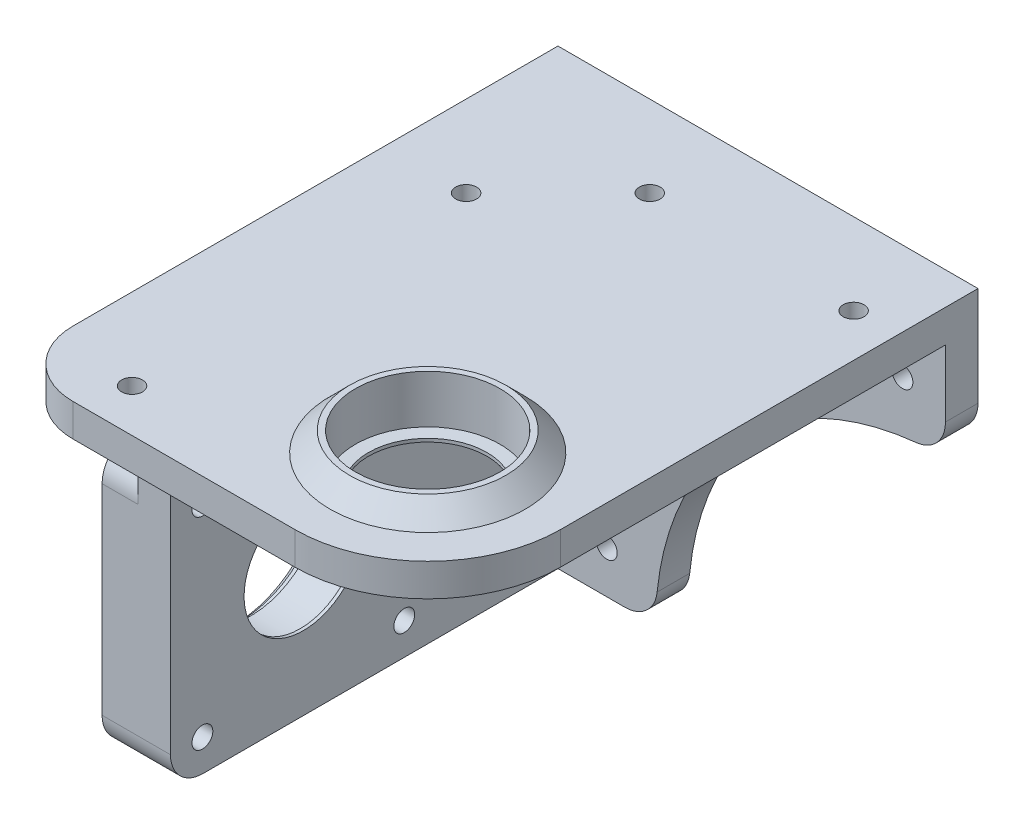
SolidWorks part; units mm, degrees
ref_plane "Front Plane" through (0, 0, 0) normal (0, 0, 1) x (1, 0, 0)
ref_plane "Top Plane" through (0, 0, 0) normal (0, 1, 0) x (1, 0, 0)
ref_plane "Right Plane" through (0, 0, 0) normal (1, 0, 0) x (0, 0, -1)
sketch "Sketch1" plane through (0, 0, 0) normal (0, 0, 1) x (1, 0, 0)
  line L0 (-1060.6916, 12.25) -> (48939.3083, 12.25) construction
  line L1 (-32.25, -32.25) -> (-16.9968, -32.25)
  line L2 (-32.25, -32.25) -> (-32.25, 32.25)
  line L3 (-32.25, 32.25) -> (32.25, 32.25)
  line L4 (32.25, 16.9968) -> (32.25, 32.25)
  line L5 (-32.25, -32.25) -> (32.25, 32.25) construction
  line L6 (-32.25, 32.25) -> (32.25, -32.25) construction
  line L7 (-12.25, -1023.3214) -> (-12.25, 48976.6786) construction
  line L8 (-1048.9078, 19.75) -> (48951.0922, 19.75) construction
  line L9 (-19.75, -955.4396) -> (-19.75, 49044.5604) construction
  arc A0 (27.7551, 12.0224) -> (-12.0224, -27.7551) centre (32.25, -32.25) ccw
  circle A1 centre (-19.75, 19.75) radius 1.6
  circle A2 centre (-5.65, 19.75) radius 1.6
  circle A3 centre (25.65, 19.75) radius 1.6
  circle A4 centre (-19.75, 5.65) radius 1.6
  circle A5 centre (-19.75, -25.65) radius 1.6
  arc A6 (27.7551, 12.0224) -> (32.25, 16.9968) centre (27.25, 16.9968) ccw
  arc A7 (-12.0224, -27.7551) -> (-16.9968, -32.25) centre (-16.9968, -27.25) cw
  point P0 (0, 0)
  point P28 (32.25, 12.25)
  point P31 (-12.25, -32.25)
  dimension "D4" = 7.5
  dimension "D6" = 3.2
  dimension "D8" = 5
  dimension "D9" = 5
  dimension "D10" = 5
  dimension "D11" = 5
  dimension "D1" = 64.5
  dimension "D2" = 20
  dimension "D3" = 20
  dimension "D5" = 7.5
  dimension "D7" = 5
extrude "Boss-Extrude1" add sketch "Sketch1" along normal blind 5
sketch "Sketch2" plane through (0, 0, 5) normal (0, 0, 1) x (1, 0, 0)
  line L0 (32.25, 16.9968) -> (32.25, 32.25) construction
  line L1 (-32.25, 32.25) -> (32.25, 32.25)
  line L2 (-32.25, 32.25) -> (-32.25, 27.25)
  line L3 (-27.25, 27.25) -> (32.25, 27.25)
  line L4 (32.25, 32.25) -> (32.25, 27.25)
  line L5 (-32.25, -32.25) -> (-16.9968, -32.25) construction
  line L7 (-32.25, 27.25) -> (-32.25, -32.25)
  line L8 (-32.25, -32.25) -> (-27.25, -32.25)
  line L9 (-27.25, 27.25) -> (-27.25, -32.25)
  dimension "D1" = 5
extrude "Boss-Extrude2" add sketch "Sketch2" along normal blind 79.5
sketch "Sketch3" plane through (0, 32.25, 0) normal (0, 1, 0) x (1, 0, 0)
  line L2 (32.25, -84.5) -> (-32.25, -84.5) construction
  line L3 (32.25, -84.5) -> (32.25, 0) construction
  line L4 (11.85, -84.5) -> (11.85, -91.4766)
  line L5 (11.85, -91.4766) -> (44.1004, -91.4766)
  line L6 (44.1004, -91.4766) -> (44.1004, -64.1)
  line L7 (44.1004, -64.1) -> (32.25, -64.1)
  circle A0 centre (11.85, -64.1) radius 15 construction
  arc A1 (11.85, -84.5) -> (32.25, -64.1) centre (11.85, -64.1) ccw
  circle A2 centre (11.85, -64.1) radius 11.1
  dimension "D1" = 30
  dimension "D2" = 5.4
  dimension "D3" = 22.2
extrude "Cut-Extrude1" cut sketch "Sketch3" against normal through all
sketch "Sketch4" plane through (0, 32.25, 0) normal (0, 1, 0) x (1, 0, 0)
  circle A0 centre (11.85, -64.1) radius 15
  circle A1 centre (11.85, -64.1) radius 15 construction
  circle A2 centre (11.85, -64.1) radius 11.1
  circle A3 centre (11.85, -64.1) radius 11.1 construction
extrude "Boss-Extrude3" add sketch "Sketch4" along normal blind 3
chamfer "Chamfer1" distance 3 angle 45 1 edges at (11.85, 35.25, 79.1)
sketch "Sketch5" plane through (0, 27.25, 0) normal (0, -1, 0) x (1, 0, 0)
  circle A0 centre (11.85, 64.1) radius 11.1
  circle A1 centre (11.85, 64.1) radius 9.1
  circle A2 centre (11.85, 64.1) radius 11.1 construction
  dimension "D1" = 2
extrude "Boss-Extrude4" add sketch "Sketch5" against normal blind 1
chamfer "Chamfer2" distance 0.5 distance2 10 1 edges at (11.85, 28.25, 55)
sketch "Sketch6" plane through (0, 32.25, 0) normal (0, 1, 0) x (1, 0, 0)
  line L0 (-1014.3468, -12.5) -> (48985.6532, -12.5) construction
  line L1 (-19.75, -1047.3352) -> (-19.75, 48952.6648) construction
  line L2 (32.25, 0) -> (-32.25, 0) construction
  line L3 (-32.25, -84.5) -> (-32.25, 0) construction
  line L4 (-1001.8593, -20) -> (48998.1407, -20) construction
  line L5 (-12.25, -974.0532) -> (-12.25, 49025.9468) construction
  line L9 (11.85, -84.5) -> (-32.25, -84.5) construction
  circle A0 centre (-19.75, -26.6) radius 1.6
  circle A1 centre (-19.75, -77.9) radius 1.6
  circle A2 centre (-5.65, -12.5) radius 1.6
  circle A3 centre (25.65, -12.5) radius 1.6
  dimension "D5" = 3.2
  dimension "D6" = 5
  dimension "D7" = 5
  dimension "D1" = 12.5
  dimension "D2" = 12.5
  dimension "D3" = 7.5
  dimension "D4" = 7.5
extrude "Cut-Extrude2" cut sketch "Sketch6" against normal through all
sketch "Sketch7" plane through (-32.25, 0, 0) normal (-1, 0, 0) x (0, 0, 1)
  line L0 (64.5, -32.25) -> (64.5, 19.75)
  line L1 (84.5, -32.25) -> (0, -32.25) construction
  line L2 (0, 32.25) -> (0, -32.25) construction
  line L3 (72, 27.25) -> (84.5, 27.25)
  line L4 (84.5, 27.25) -> (84.5, -32.25)
  line L5 (64.5, -32.25) -> (84.5, -32.25)
  line L6 (84.5, 32.25) -> (84.5, -32.25) construction
  line L7 (84.5, 32.25) -> (0, 32.25) construction
  line L8 (-984.8674, 19.75) -> (49015.1326, 19.75) construction
  line L9 (-988.0043, 12.25) -> (49011.9957, 12.25) construction
  line L10 (12.5, -945.2547) -> (12.5, 49054.7453) construction
  line L11 (20, -945.3003) -> (20, 49054.6997) construction
  line L12 (0, -201023.3214) -> (0, 248976.6786) construction
  line L14 (28.6, -27.35) -> (59.6, -27.35) construction
  line L15 (28.6, -27.35) -> (28.6, 3.65) construction
  line L16 (28.6, 3.65) -> (59.6, 3.65) construction
  line L17 (59.6, -27.35) -> (59.6, 3.65) construction
  line L18 (28.6, -27.35) -> (59.6, 3.65) construction
  line L19 (28.6, 3.65) -> (59.6, -27.35) construction
  circle A0 centre (44.1, -11.85) radius 15 construction
  circle A1 centre (44.1, -11.85) radius 11.1
  circle A2 centre (28.6, -27.35) radius 1.6
  arc A3 (64.5, 19.75) -> (72, 27.25) centre (72, 19.75) cw
  circle A4 centre (57.9, 19.75) radius 1.6
  circle A5 centre (26.6, 19.75) radius 1.6
  circle A6 centre (12.5, 5.65) radius 1.6
  circle A7 centre (12.5, -25.65) radius 1.6
  circle A8 centre (28.6, 3.65) radius 1.6
  circle A9 centre (59.6, 3.65) radius 1.6
  circle A10 centre (59.6, -27.35) radius 1.6
  dimension "D3" = 30
  dimension "D6" = 22.2
  dimension "D11" = 7.5
  dimension "D12" = 3.2
  dimension "D14" = 64.5
  dimension "D16" = 5
  dimension "D5" = 5.4
  dimension "D17" = 5
  dimension "D19" = 3.2
  dimension "D2" = 5
  dimension "D4" = 5.4
  dimension "D7" = 12.5
  dimension "D8" = 7.5
  dimension "D9" = 12.5
  dimension "D10" = 7.5
  dimension "D13" = 5
  dimension "D15" = 5
  dimension "D18" = 31
extrude "Cut-Extrude3" cut sketch "Sketch7" against normal through all
sketch "Sketch8" plane through (-27.25, 0, 0) normal (1, 0, 0) x (0, 0, -1)
  circle A0 centre (-44.1, -11.85) radius 9.1
  circle A1 centre (-44.1, -11.85) radius 11.1 construction
  circle A2 centre (-44.1, -11.85) radius 11.1
  dimension "D1" = 2
extrude "Boss-Extrude5" add sketch "Sketch8" against normal blind 1
chamfer "Chamfer3" distance 0.5 distance2 10 1 edges at (-28.25, -2.75, 44.1)
sketch "Sketch9" plane through (-32.25, 0, 0) normal (-1, 0, 0) x (0, 0, 1)
  line L0 (64.5, -32.25) -> (0, -32.25) construction
  line L1 (64.5, -32.25) -> (23.7, -32.25)
  line L2 (64.5, -32.25) -> (64.5, 8.55)
  line L3 (64.5, 8.55) -> (23.7, 8.55)
  line L5 (64.5, -32.25) -> (23.7, 8.55) construction
  line L6 (64.5, 8.55) -> (23.7, -32.25) construction
  line L7 (64.5, -32.25) -> (64.5, 19.75) construction
  line L8 (64.5, -32.25) -> (0, -32.25) construction
  line L9 (23.7, 8.55) -> (18.2, 8.55)
  line L11 (23.7, -32.25) -> (18.2, -32.25)
  line L12 (18.2, 8.55) -> (18.2, -32.25)
  circle A0 centre (28.6, -27.35) radius 1.6
  circle A1 centre (28.6, 3.65) radius 1.6
  circle A2 centre (44.1, -11.85) radius 11.1
  circle A3 centre (44.1, -11.85) radius 11.1 construction
  circle A4 centre (59.6, 3.65) radius 1.6
  circle A5 centre (59.6, -27.35) radius 1.6
  circle A6 centre (28.6, -27.35) radius 1.6 construction
  circle A7 centre (28.6, 3.65) radius 1.6 construction
  circle A8 centre (59.6, -27.35) radius 1.6 construction
  circle A9 centre (59.6, 3.65) radius 1.6 construction
  dimension "D1" = 5.5
extrude "Boss-Extrude6" add sketch "Sketch9" along normal blind 5.5
sketch "Sketch10" plane through (-37.75, 0, 0) normal (-1, 0, 0) x (0, 0, 1)
  circle A0 centre (44.1, -11.85) radius 12.5
  dimension "D1" = 25
extrude "Cut-Extrude4" cut sketch "Sketch10" against normal blind 2.5
chamfer "Chamfer6" distance 1 angle 45 1 edges at (-37.75, -11.85, 56.6)
chamfer "Chamfer5" distance 5.5 angle 45 1 edges at (-37.75, -11.85, 18.2)
fillet "Fillet4" radius 5 1 edges at (-32.5, -32.25, 64.5)
fillet "Fillet5" radius 5 1 edges
fillet "Fillet6" radius 5 1 edges at (-35, 8.55, 20.95)
fillet "Fillet7" radius 5 1 edges
fillet "Fillet1" radius 10 1 edges at (-32.25, 29.75, 84.5)
